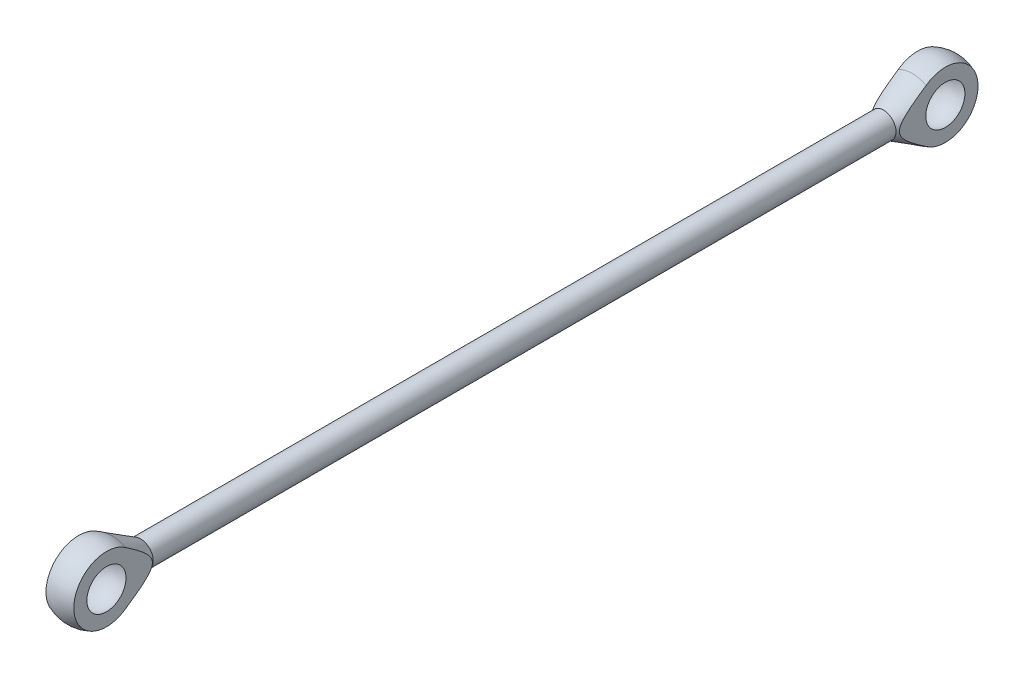
SolidWorks part; units mm, degrees
ref_plane "Front Plane" through (0, 0, 0) normal (0, 0, 1) x (1, 0, 0)
ref_plane "Top Plane" through (0, 0, 0) normal (0, 1, 0) x (1, 0, 0)
ref_plane "Right Plane" through (0, 0, 0) normal (1, 0, 0) x (0, 0, -1)
sketch "Sketch3" plane through (0, 0, 0) normal (0, 0, 1) x (1, 0, 0)
  circle A0 centre (0, 0) radius 5
  dimension "D1" = 10
extrude "Boss-Extrude2" add sketch "Sketch3" along normal blind 332
sketch "Sketch4" plane through (0, 0, 0) normal (0, 1, 0) x (1, 0, 0)
  line L0 (-5, -166) -> (138.2976, -166) construction
  line L1 (-5, 0) -> (-5, -332) construction
  line L2 (-14.05, 0) -> (14.05, 0) construction
  line L3 (-14.05, 0) -> (14.05, 0)
  line L4 (-14.05, -332) -> (14.05, -332)
  arc A2 (14.05, 0) -> (-14.05, 0) centre (0, 0) ccw
  arc A3 (14.05, -332) -> (-14.05, -332) centre (0, -332) cw
revolve "Revolve10" add sketch "Sketch4" angle 360 about L4 region at (0, 0, 337.963)
revolve "Revolve11" add sketch "Sketch4<6>" angle 360 about L3 region at (0, 0, -5.963)
sketch "Sketch4<6>" plane through (0, 0, 0) normal (0, 1, 0) x (1, 0, 0) same geometry as "Sketch4"
sketch "Sketch8" plane through (0, 0, 0) normal (0, 1, 0) x (1, 0, 0)
  line L0 (0, 18.7604) -> (0, -27.3381) construction
  line L1 (0, -6.8087) -> (12.29, -6.8087)
  line L4 (5, -19.01) -> (12.29, -6.8087)
  line L6 (-5, -166) -> (43.063, -166) construction
  line L7 (-5, -13.1302) -> (-5, -318.8698) construction
  line L12 (0, -19.01) -> (5, -19.01)
  line L13 (5, -318.8698) -> (5, -13.1302) construction
  line L14 (0, -19.01) -> (0, -6.8087)
  line L21 (0, -312.99) -> (5, -312.99)
  line L22 (0, -312.99) -> (0, -325.1913)
  line L23 (0, -325.1913) -> (12.29, -325.1913)
  line L24 (5, -312.99) -> (12.29, -325.1913)
  circle A0 centre (0, 0) radius 14.05 construction
  dimension "D3" = 28.1
  dimension "D1" = 19.01
  dimension "D2" = 12.29
revolve "Revolve12" add sketch "Sketch8" angle 360 about L14 region at (4.5786, 0, 12.0519)
revolve "Revolve13" add sketch "Sketch8<3>" angle 360 about L22 region at (4.5786, 0, 319.9481)
sketch "Sketch8<3>" plane through (0, 0, 0) normal (0, 1, 0) x (1, 0, 0) same geometry as "Sketch8"
sketch "Sketch7" plane through (0, 0, 0) normal (1, 0, 0) x (0, 0, -1)
  line L0 (-166, -5) -> (-166, 41.4272) construction
  line L1 (-312.99, -5) -> (-19.01, -5) construction
  circle A0 centre (0, 0) radius 24.0936
  circle A1 centre (-332, 0) radius 24.0936
extrude "Cut-Extrude1" cut sketch "Sketch7" against normal through all from offset 5.5 offset against normal yes
extrude "Cut-Extrude2" cut sketch "Sketch7<2>" along normal through all from offset 5.5
sketch "Sketch7<2>" plane through (0, 0, 0) normal (1, 0, 0) x (0, 0, -1) same geometry as "Sketch7"
sketch "Sketch6" plane through (0, 0, 0) normal (0, 1, 0) x (1, 0, 0)
  line L0 (-19.1413, 0) -> (35.2978, 0) construction
  line L1 (-9.5, 0) -> (9.5, 0)
  line L2 (-5, -166) -> (57.846, -166) construction
  line L3 (-5, -19.01) -> (-5, -312.99) construction
  line L4 (-9.5, -332) -> (9.5, -332)
  arc A1 (9.5, 0) -> (-9.5, 0) centre (0, 0) ccw
  arc A2 (9.5, -332) -> (-9.5, -332) centre (0, -332) cw
  dimension "D1" = 19
revolve "Cut-Revolve1" cut sketch "Sketch6" angle 360 about L1 region at (0, 0, -4.0319)
revolve "Cut-Revolve2" cut sketch "Sketch6<3>" angle 360 about L4
sketch "Sketch6<3>" plane through (0, 0, 0) normal (0, 1, 0) x (1, 0, 0) same geometry as "Sketch6"
